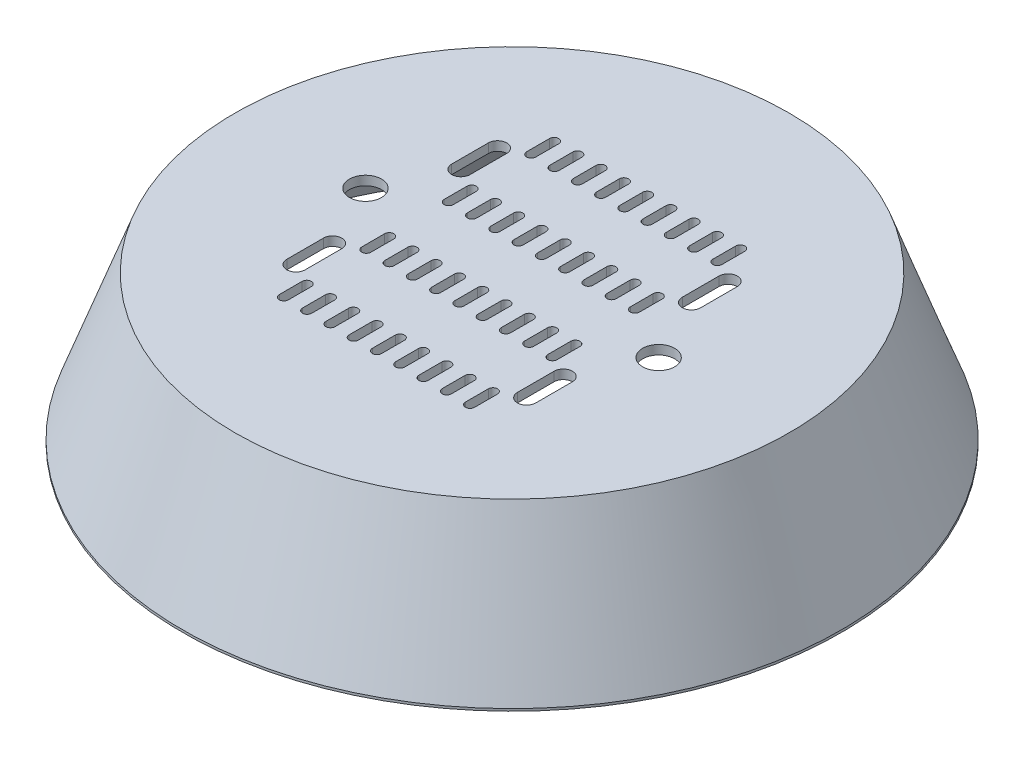
SolidWorks part; units mm, degrees
ref_plane "Alzado" through (0, 0, 0) normal (0, 0, 1) x (1, 0, 0)
ref_plane "Planta" through (0, 0, 0) normal (0, 1, 0) x (1, 0, 0)
ref_plane "Vista lateral" through (0, 0, 0) normal (1, 0, 0) x (0, 0, -1)
sketch "Croquis1" plane through (0, 0, 0) normal (0, 0, 1) x (1, 0, 0)
  line L0 (0, 0) -> (40, 0)
  line L1 (40, 0) -> (59.0809, 0)
  line L2 (59.0809, 0) -> (70, -30)
  line L3 (70, -30) -> (71.9464, -30)
  line L4 (71.9464, -30) -> (71.9464, -29.5)
  line L5 (71.9464, -29.5) -> (60.4813, 2)
  line L6 (0, 2) -> (40, 2)
  line L7 (60.4813, 2) -> (40, 2)
  line L10 (0, 0) -> (0, 2)
  line L13 (40.328, 0) -> (70.6428, 0) construction
  line L14 (70.6428, 0) -> (70.2018, 1.0584) construction
  line L15 (40, 0) -> (40.328, 0) construction
  line L16 (40.328, 2) -> (68.4374, 2) construction
  line L17 (68.4374, 2) -> (68.4374, 2) construction
  line L18 (40, 2) -> (40.328, 2) construction
  dimension "D6" = 0.5
  dimension "D1" = 40
  dimension "D2" = 2
  dimension "D3" = 110
  dimension "D4" = 30
  dimension "D7" = 70
  dimension "D5" = 2
revolve "Revolución1" add sketch "Croquis1" angle 360 about L10
sketch "Croquis3" plane through (0, 2, 0) normal (0, 1, 0) x (1, 0, 0)
  circle A0 centre (-32, 0) radius 3.5
  circle A1 centre (32, 0) radius 3.5
  circle A2 centre (0, 0) radius 32 construction
  dimension "D1" = 7
  dimension "D2" = 64
extrude "Cortar-Extruir1" cut sketch "Croquis3" against normal up to next
sketch "Croquis4" plane through (0, 2, 0) normal (0, 1, 0) x (1, 0, 0)
  line L0 (0, 2.5) -> (0, -2.5) construction
  line L1 (1, 2.5) -> (1, -2.5) construction
  line L2 (-1, 2.5) -> (-1, -2.5) construction
  line L3 (5.08, 2.5) -> (5.08, -2.5) construction
  line L4 (6.08, 2.5) -> (6.08, -2.5) construction
  line L5 (4.08, 2.5) -> (4.08, -2.5) construction
  line L6 (10.16, 2.5) -> (10.16, -2.5) construction
  line L7 (11.16, 2.5) -> (11.16, -2.5) construction
  line L8 (9.16, 2.5) -> (9.16, -2.5) construction
  line L9 (15.24, 2.5) -> (15.24, -2.5) construction
  line L10 (16.24, 2.5) -> (16.24, -2.5) construction
  line L11 (14.24, 2.5) -> (14.24, -2.5) construction
  line L12 (20.32, 2.5) -> (20.32, -2.5) construction
  line L13 (21.32, 2.5) -> (21.32, -2.5) construction
  line L14 (19.32, 2.5) -> (19.32, -2.5) construction
  line L15 (-5.08, 2.5) -> (-5.08, -2.5) construction
  line L16 (-4.08, 2.5) -> (-4.08, -2.5) construction
  line L17 (-6.08, 2.5) -> (-6.08, -2.5) construction
  line L18 (-10.16, 2.5) -> (-10.16, -2.5) construction
  line L19 (-9.16, 2.5) -> (-9.16, -2.5) construction
  line L20 (-11.16, 2.5) -> (-11.16, -2.5) construction
  line L21 (-15.24, 2.5) -> (-15.24, -2.5) construction
  line L22 (-14.24, 2.5) -> (-14.24, -2.5) construction
  line L23 (-16.24, 2.5) -> (-16.24, -2.5) construction
  line L24 (-20.32, 2.5) -> (-20.32, -2.5) construction
  line L25 (-19.32, 2.5) -> (-19.32, -2.5) construction
  line L26 (-21.32, 2.5) -> (-21.32, -2.5) construction
  line L27 (0, 11.5) -> (0, 6.5) construction
  line L28 (1, 11.5) -> (1, 6.5)
  line L29 (-1, 11.5) -> (-1, 6.5)
  line L30 (5.08, 11.5) -> (5.08, 6.5) construction
  line L31 (6.08, 11.5) -> (6.08, 6.5)
  line L32 (4.08, 11.5) -> (4.08, 6.5)
  line L33 (10.16, 11.5) -> (10.16, 6.5) construction
  line L34 (11.16, 11.5) -> (11.16, 6.5)
  line L35 (9.16, 11.5) -> (9.16, 6.5)
  line L36 (15.24, 11.5) -> (15.24, 6.5) construction
  line L37 (16.24, 11.5) -> (16.24, 6.5)
  line L38 (14.24, 11.5) -> (14.24, 6.5)
  line L39 (20.32, 11.5) -> (20.32, 6.5) construction
  line L40 (21.32, 11.5) -> (21.32, 6.5)
  line L41 (19.32, 11.5) -> (19.32, 6.5)
  line L42 (-5.08, 11.5) -> (-5.08, 6.5) construction
  line L43 (-4.08, 11.5) -> (-4.08, 6.5)
  line L44 (-6.08, 11.5) -> (-6.08, 6.5)
  line L45 (-10.16, 11.5) -> (-10.16, 6.5) construction
  line L46 (-9.16, 11.5) -> (-9.16, 6.5)
  line L47 (-11.16, 11.5) -> (-11.16, 6.5)
  line L48 (-15.24, 11.5) -> (-15.24, 6.5) construction
  line L49 (-14.24, 11.5) -> (-14.24, 6.5)
  line L50 (-16.24, 11.5) -> (-16.24, 6.5)
  line L51 (-20.32, 11.5) -> (-20.32, 6.5) construction
  line L52 (-19.32, 11.5) -> (-19.32, 6.5)
  line L53 (-21.32, 11.5) -> (-21.32, 6.5)
  line L54 (0, 20.5) -> (0, 15.5) construction
  line L55 (1, 20.5) -> (1, 15.5) construction
  line L56 (-1, 20.5) -> (-1, 15.5) construction
  line L57 (5.08, 20.5) -> (5.08, 15.5) construction
  line L58 (6.08, 20.5) -> (6.08, 15.5) construction
  line L59 (4.08, 20.5) -> (4.08, 15.5) construction
  line L60 (10.16, 20.5) -> (10.16, 15.5) construction
  line L61 (11.16, 20.5) -> (11.16, 15.5) construction
  line L62 (9.16, 20.5) -> (9.16, 15.5) construction
  line L63 (15.24, 20.5) -> (15.24, 15.5) construction
  line L64 (16.24, 20.5) -> (16.24, 15.5) construction
  line L65 (14.24, 20.5) -> (14.24, 15.5) construction
  line L66 (20.32, 20.5) -> (20.32, 15.5) construction
  line L67 (21.32, 20.5) -> (21.32, 15.5) construction
  line L68 (19.32, 20.5) -> (19.32, 15.5) construction
  line L69 (-5.08, 20.5) -> (-5.08, 15.5) construction
  line L70 (-4.08, 20.5) -> (-4.08, 15.5) construction
  line L71 (-6.08, 20.5) -> (-6.08, 15.5) construction
  line L72 (-10.16, 20.5) -> (-10.16, 15.5) construction
  line L73 (-9.16, 20.5) -> (-9.16, 15.5) construction
  line L74 (-11.16, 20.5) -> (-11.16, 15.5) construction
  line L75 (-15.24, 20.5) -> (-15.24, 15.5) construction
  line L76 (-14.24, 20.5) -> (-14.24, 15.5) construction
  line L77 (-16.24, 20.5) -> (-16.24, 15.5) construction
  line L78 (-20.32, 20.5) -> (-20.32, 15.5) construction
  line L79 (-19.32, 20.5) -> (-19.32, 15.5) construction
  line L80 (-21.32, 20.5) -> (-21.32, 15.5) construction
  line L81 (0, 29.5) -> (0, 24.5) construction
  line L82 (1, 29.5) -> (1, 24.5)
  line L83 (-1, 29.5) -> (-1, 24.5)
  line L84 (5.08, 29.5) -> (5.08, 24.5) construction
  line L85 (6.08, 29.5) -> (6.08, 24.5)
  line L86 (4.08, 29.5) -> (4.08, 24.5)
  line L87 (10.16, 29.5) -> (10.16, 24.5) construction
  line L88 (11.16, 29.5) -> (11.16, 24.5)
  line L89 (9.16, 29.5) -> (9.16, 24.5)
  line L90 (15.24, 29.5) -> (15.24, 24.5) construction
  line L91 (16.24, 29.5) -> (16.24, 24.5)
  line L92 (14.24, 29.5) -> (14.24, 24.5)
  line L93 (20.32, 29.5) -> (20.32, 24.5) construction
  line L94 (21.32, 29.5) -> (21.32, 24.5)
  line L95 (19.32, 29.5) -> (19.32, 24.5)
  line L96 (-5.08, 29.5) -> (-5.08, 24.5) construction
  line L97 (-4.08, 29.5) -> (-4.08, 24.5)
  line L98 (-6.08, 29.5) -> (-6.08, 24.5)
  line L99 (-10.16, 29.5) -> (-10.16, 24.5) construction
  line L100 (-9.16, 29.5) -> (-9.16, 24.5)
  line L101 (-11.16, 29.5) -> (-11.16, 24.5)
  line L102 (-15.24, 29.5) -> (-15.24, 24.5) construction
  line L103 (-14.24, 29.5) -> (-14.24, 24.5)
  line L104 (-16.24, 29.5) -> (-16.24, 24.5)
  line L105 (-20.32, 29.5) -> (-20.32, 24.5) construction
  line L106 (-19.32, 29.5) -> (-19.32, 24.5)
  line L107 (-21.32, 29.5) -> (-21.32, 24.5)
  line L108 (0, -6.5) -> (0, -11.5) construction
  line L109 (1, -6.5) -> (1, -11.5)
  line L110 (-1, -6.5) -> (-1, -11.5)
  line L111 (5.08, -6.5) -> (5.08, -11.5) construction
  line L112 (6.08, -6.5) -> (6.08, -11.5)
  line L113 (4.08, -6.5) -> (4.08, -11.5)
  line L114 (10.16, -6.5) -> (10.16, -11.5) construction
  line L115 (11.16, -6.5) -> (11.16, -11.5)
  line L116 (9.16, -6.5) -> (9.16, -11.5)
  line L117 (15.24, -6.5) -> (15.24, -11.5) construction
  line L118 (16.24, -6.5) -> (16.24, -11.5)
  line L119 (14.24, -6.5) -> (14.24, -11.5)
  line L120 (20.32, -6.5) -> (20.32, -11.5) construction
  line L121 (21.32, -6.5) -> (21.32, -11.5)
  line L122 (19.32, -6.5) -> (19.32, -11.5)
  line L123 (-5.08, -6.5) -> (-5.08, -11.5) construction
  line L124 (-4.08, -6.5) -> (-4.08, -11.5)
  line L125 (-6.08, -6.5) -> (-6.08, -11.5)
  line L126 (-10.16, -6.5) -> (-10.16, -11.5) construction
  line L127 (-9.16, -6.5) -> (-9.16, -11.5)
  line L128 (-11.16, -6.5) -> (-11.16, -11.5)
  line L129 (-15.24, -6.5) -> (-15.24, -11.5) construction
  line L130 (-14.24, -6.5) -> (-14.24, -11.5)
  line L131 (-16.24, -6.5) -> (-16.24, -11.5)
  line L132 (-20.32, -6.5) -> (-20.32, -11.5) construction
  line L133 (-19.32, -6.5) -> (-19.32, -11.5)
  line L134 (-21.32, -6.5) -> (-21.32, -11.5)
  line L135 (0, -15.5) -> (0, -20.5) construction
  line L136 (1, -15.5) -> (1, -20.5) construction
  line L137 (-1, -15.5) -> (-1, -20.5) construction
  line L138 (5.08, -15.5) -> (5.08, -20.5) construction
  line L139 (6.08, -15.5) -> (6.08, -20.5) construction
  line L140 (4.08, -15.5) -> (4.08, -20.5) construction
  line L141 (10.16, -15.5) -> (10.16, -20.5) construction
  line L142 (11.16, -15.5) -> (11.16, -20.5) construction
  line L143 (9.16, -15.5) -> (9.16, -20.5) construction
  line L144 (15.24, -15.5) -> (15.24, -20.5) construction
  line L145 (16.24, -15.5) -> (16.24, -20.5) construction
  line L146 (14.24, -15.5) -> (14.24, -20.5) construction
  line L147 (20.32, -15.5) -> (20.32, -20.5) construction
  line L148 (21.32, -15.5) -> (21.32, -20.5) construction
  line L149 (19.32, -15.5) -> (19.32, -20.5) construction
  line L150 (-5.08, -15.5) -> (-5.08, -20.5) construction
  line L151 (-4.08, -15.5) -> (-4.08, -20.5) construction
  line L152 (-6.08, -15.5) -> (-6.08, -20.5) construction
  line L153 (-10.16, -15.5) -> (-10.16, -20.5) construction
  line L154 (-9.16, -15.5) -> (-9.16, -20.5) construction
  line L155 (-11.16, -15.5) -> (-11.16, -20.5) construction
  line L156 (-15.24, -15.5) -> (-15.24, -20.5) construction
  line L157 (-14.24, -15.5) -> (-14.24, -20.5) construction
  line L158 (-16.24, -15.5) -> (-16.24, -20.5) construction
  line L159 (-20.32, -15.5) -> (-20.32, -20.5) construction
  line L160 (-19.32, -15.5) -> (-19.32, -20.5) construction
  line L161 (-21.32, -15.5) -> (-21.32, -20.5) construction
  line L162 (0, -24.5) -> (0, -29.5) construction
  line L163 (1, -24.5) -> (1, -29.5)
  line L164 (-1, -24.5) -> (-1, -29.5)
  line L165 (5.08, -24.5) -> (5.08, -29.5) construction
  line L166 (6.08, -24.5) -> (6.08, -29.5)
  line L167 (4.08, -24.5) -> (4.08, -29.5)
  line L168 (10.16, -24.5) -> (10.16, -29.5) construction
  line L169 (11.16, -24.5) -> (11.16, -29.5)
  line L170 (9.16, -24.5) -> (9.16, -29.5)
  line L171 (15.24, -24.5) -> (15.24, -29.5) construction
  line L172 (16.24, -24.5) -> (16.24, -29.5)
  line L173 (14.24, -24.5) -> (14.24, -29.5)
  line L174 (20.32, -24.5) -> (20.32, -29.5) construction
  line L175 (21.32, -24.5) -> (21.32, -29.5)
  line L176 (19.32, -24.5) -> (19.32, -29.5)
  line L177 (-5.08, -24.5) -> (-5.08, -29.5) construction
  line L178 (-4.08, -24.5) -> (-4.08, -29.5)
  line L179 (-6.08, -24.5) -> (-6.08, -29.5)
  line L180 (-10.16, -24.5) -> (-10.16, -29.5) construction
  line L181 (-9.16, -24.5) -> (-9.16, -29.5)
  line L182 (-11.16, -24.5) -> (-11.16, -29.5)
  line L183 (-15.24, -24.5) -> (-15.24, -29.5) construction
  line L184 (-14.24, -24.5) -> (-14.24, -29.5)
  line L185 (-16.24, -24.5) -> (-16.24, -29.5)
  line L186 (-20.32, -24.5) -> (-20.32, -29.5) construction
  line L187 (-19.32, -24.5) -> (-19.32, -29.5)
  line L188 (-21.32, -24.5) -> (-21.32, -29.5)
  arc A0 (1, 2.5) -> (-1, 2.5) centre (0, 2.5) ccw construction
  arc A1 (-1, -2.5) -> (1, -2.5) centre (0, -2.5) ccw construction
  arc A2 (6.08, 2.5) -> (4.08, 2.5) centre (5.08, 2.5) ccw construction
  arc A3 (4.08, -2.5) -> (6.08, -2.5) centre (5.08, -2.5) ccw construction
  arc A4 (11.16, 2.5) -> (9.16, 2.5) centre (10.16, 2.5) ccw construction
  arc A5 (9.16, -2.5) -> (11.16, -2.5) centre (10.16, -2.5) ccw construction
  arc A6 (16.24, 2.5) -> (14.24, 2.5) centre (15.24, 2.5) ccw construction
  arc A7 (14.24, -2.5) -> (16.24, -2.5) centre (15.24, -2.5) ccw construction
  arc A8 (21.32, 2.5) -> (19.32, 2.5) centre (20.32, 2.5) ccw construction
  arc A9 (19.32, -2.5) -> (21.32, -2.5) centre (20.32, -2.5) ccw construction
  arc A10 (-4.08, 2.5) -> (-6.08, 2.5) centre (-5.08, 2.5) ccw construction
  arc A11 (-6.08, -2.5) -> (-4.08, -2.5) centre (-5.08, -2.5) ccw construction
  arc A12 (-9.16, 2.5) -> (-11.16, 2.5) centre (-10.16, 2.5) ccw construction
  arc A13 (-11.16, -2.5) -> (-9.16, -2.5) centre (-10.16, -2.5) ccw construction
  arc A14 (-14.24, 2.5) -> (-16.24, 2.5) centre (-15.24, 2.5) ccw construction
  arc A15 (-16.24, -2.5) -> (-14.24, -2.5) centre (-15.24, -2.5) ccw construction
  arc A16 (-19.32, 2.5) -> (-21.32, 2.5) centre (-20.32, 2.5) ccw construction
  arc A17 (-21.32, -2.5) -> (-19.32, -2.5) centre (-20.32, -2.5) ccw construction
  arc A18 (1, 11.5) -> (-1, 11.5) centre (0, 11.5) ccw
  arc A19 (-1, 6.5) -> (1, 6.5) centre (0, 6.5) ccw
  arc A20 (6.08, 11.5) -> (4.08, 11.5) centre (5.08, 11.5) ccw
  arc A21 (4.08, 6.5) -> (6.08, 6.5) centre (5.08, 6.5) ccw
  arc A22 (11.16, 11.5) -> (9.16, 11.5) centre (10.16, 11.5) ccw
  arc A23 (9.16, 6.5) -> (11.16, 6.5) centre (10.16, 6.5) ccw
  arc A24 (16.24, 11.5) -> (14.24, 11.5) centre (15.24, 11.5) ccw
  arc A25 (14.24, 6.5) -> (16.24, 6.5) centre (15.24, 6.5) ccw
  arc A26 (21.32, 11.5) -> (19.32, 11.5) centre (20.32, 11.5) ccw
  arc A27 (19.32, 6.5) -> (21.32, 6.5) centre (20.32, 6.5) ccw
  arc A28 (-4.08, 11.5) -> (-6.08, 11.5) centre (-5.08, 11.5) ccw
  arc A29 (-6.08, 6.5) -> (-4.08, 6.5) centre (-5.08, 6.5) ccw
  arc A30 (-9.16, 11.5) -> (-11.16, 11.5) centre (-10.16, 11.5) ccw
  arc A31 (-11.16, 6.5) -> (-9.16, 6.5) centre (-10.16, 6.5) ccw
  arc A32 (-14.24, 11.5) -> (-16.24, 11.5) centre (-15.24, 11.5) ccw
  arc A33 (-16.24, 6.5) -> (-14.24, 6.5) centre (-15.24, 6.5) ccw
  arc A34 (-19.32, 11.5) -> (-21.32, 11.5) centre (-20.32, 11.5) ccw
  arc A35 (-21.32, 6.5) -> (-19.32, 6.5) centre (-20.32, 6.5) ccw
  arc A36 (1, 20.5) -> (-1, 20.5) centre (0, 20.5) ccw construction
  arc A37 (-1, 15.5) -> (1, 15.5) centre (0, 15.5) ccw construction
  arc A38 (6.08, 20.5) -> (4.08, 20.5) centre (5.08, 20.5) ccw construction
  arc A39 (4.08, 15.5) -> (6.08, 15.5) centre (5.08, 15.5) ccw construction
  arc A40 (11.16, 20.5) -> (9.16, 20.5) centre (10.16, 20.5) ccw construction
  arc A41 (9.16, 15.5) -> (11.16, 15.5) centre (10.16, 15.5) ccw construction
  arc A42 (16.24, 20.5) -> (14.24, 20.5) centre (15.24, 20.5) ccw construction
  arc A43 (14.24, 15.5) -> (16.24, 15.5) centre (15.24, 15.5) ccw construction
  arc A44 (21.32, 20.5) -> (19.32, 20.5) centre (20.32, 20.5) ccw construction
  arc A45 (19.32, 15.5) -> (21.32, 15.5) centre (20.32, 15.5) ccw construction
  arc A46 (-4.08, 20.5) -> (-6.08, 20.5) centre (-5.08, 20.5) ccw construction
  arc A47 (-6.08, 15.5) -> (-4.08, 15.5) centre (-5.08, 15.5) ccw construction
  arc A48 (-9.16, 20.5) -> (-11.16, 20.5) centre (-10.16, 20.5) ccw construction
  arc A49 (-11.16, 15.5) -> (-9.16, 15.5) centre (-10.16, 15.5) ccw construction
  arc A50 (-14.24, 20.5) -> (-16.24, 20.5) centre (-15.24, 20.5) ccw construction
  arc A51 (-16.24, 15.5) -> (-14.24, 15.5) centre (-15.24, 15.5) ccw construction
  arc A52 (-19.32, 20.5) -> (-21.32, 20.5) centre (-20.32, 20.5) ccw construction
  arc A53 (-21.32, 15.5) -> (-19.32, 15.5) centre (-20.32, 15.5) ccw construction
  arc A54 (1, 29.5) -> (-1, 29.5) centre (0, 29.5) ccw
  arc A55 (-1, 24.5) -> (1, 24.5) centre (0, 24.5) ccw
  arc A56 (6.08, 29.5) -> (4.08, 29.5) centre (5.08, 29.5) ccw
  arc A57 (4.08, 24.5) -> (6.08, 24.5) centre (5.08, 24.5) ccw
  arc A58 (11.16, 29.5) -> (9.16, 29.5) centre (10.16, 29.5) ccw
  arc A59 (9.16, 24.5) -> (11.16, 24.5) centre (10.16, 24.5) ccw
  arc A60 (16.24, 29.5) -> (14.24, 29.5) centre (15.24, 29.5) ccw
  arc A61 (14.24, 24.5) -> (16.24, 24.5) centre (15.24, 24.5) ccw
  arc A62 (21.32, 29.5) -> (19.32, 29.5) centre (20.32, 29.5) ccw
  arc A63 (19.32, 24.5) -> (21.32, 24.5) centre (20.32, 24.5) ccw
  arc A64 (-4.08, 29.5) -> (-6.08, 29.5) centre (-5.08, 29.5) ccw
  arc A65 (-6.08, 24.5) -> (-4.08, 24.5) centre (-5.08, 24.5) ccw
  arc A66 (-9.16, 29.5) -> (-11.16, 29.5) centre (-10.16, 29.5) ccw
  arc A67 (-11.16, 24.5) -> (-9.16, 24.5) centre (-10.16, 24.5) ccw
  arc A68 (-14.24, 29.5) -> (-16.24, 29.5) centre (-15.24, 29.5) ccw
  arc A69 (-16.24, 24.5) -> (-14.24, 24.5) centre (-15.24, 24.5) ccw
  arc A70 (-19.32, 29.5) -> (-21.32, 29.5) centre (-20.32, 29.5) ccw
  arc A71 (-21.32, 24.5) -> (-19.32, 24.5) centre (-20.32, 24.5) ccw
  arc A72 (1, -6.5) -> (-1, -6.5) centre (0, -6.5) ccw
  arc A73 (-1, -11.5) -> (1, -11.5) centre (0, -11.5) ccw
  arc A74 (6.08, -6.5) -> (4.08, -6.5) centre (5.08, -6.5) ccw
  arc A75 (4.08, -11.5) -> (6.08, -11.5) centre (5.08, -11.5) ccw
  arc A76 (11.16, -6.5) -> (9.16, -6.5) centre (10.16, -6.5) ccw
  arc A77 (9.16, -11.5) -> (11.16, -11.5) centre (10.16, -11.5) ccw
  arc A78 (16.24, -6.5) -> (14.24, -6.5) centre (15.24, -6.5) ccw
  arc A79 (14.24, -11.5) -> (16.24, -11.5) centre (15.24, -11.5) ccw
  arc A80 (21.32, -6.5) -> (19.32, -6.5) centre (20.32, -6.5) ccw
  arc A81 (19.32, -11.5) -> (21.32, -11.5) centre (20.32, -11.5) ccw
  arc A82 (-4.08, -6.5) -> (-6.08, -6.5) centre (-5.08, -6.5) ccw
  arc A83 (-6.08, -11.5) -> (-4.08, -11.5) centre (-5.08, -11.5) ccw
  arc A84 (-9.16, -6.5) -> (-11.16, -6.5) centre (-10.16, -6.5) ccw
  arc A85 (-11.16, -11.5) -> (-9.16, -11.5) centre (-10.16, -11.5) ccw
  arc A86 (-14.24, -6.5) -> (-16.24, -6.5) centre (-15.24, -6.5) ccw
  arc A87 (-16.24, -11.5) -> (-14.24, -11.5) centre (-15.24, -11.5) ccw
  arc A88 (-19.32, -6.5) -> (-21.32, -6.5) centre (-20.32, -6.5) ccw
  arc A89 (-21.32, -11.5) -> (-19.32, -11.5) centre (-20.32, -11.5) ccw
  arc A90 (1, -15.5) -> (-1, -15.5) centre (0, -15.5) ccw construction
  arc A91 (-1, -20.5) -> (1, -20.5) centre (0, -20.5) ccw construction
  arc A92 (6.08, -15.5) -> (4.08, -15.5) centre (5.08, -15.5) ccw construction
  arc A93 (4.08, -20.5) -> (6.08, -20.5) centre (5.08, -20.5) ccw construction
  arc A94 (11.16, -15.5) -> (9.16, -15.5) centre (10.16, -15.5) ccw construction
  arc A95 (9.16, -20.5) -> (11.16, -20.5) centre (10.16, -20.5) ccw construction
  arc A96 (16.24, -15.5) -> (14.24, -15.5) centre (15.24, -15.5) ccw construction
  arc A97 (14.24, -20.5) -> (16.24, -20.5) centre (15.24, -20.5) ccw construction
  arc A98 (21.32, -15.5) -> (19.32, -15.5) centre (20.32, -15.5) ccw construction
  arc A99 (19.32, -20.5) -> (21.32, -20.5) centre (20.32, -20.5) ccw construction
  arc A100 (-4.08, -15.5) -> (-6.08, -15.5) centre (-5.08, -15.5) ccw construction
  arc A101 (-6.08, -20.5) -> (-4.08, -20.5) centre (-5.08, -20.5) ccw construction
  arc A102 (-9.16, -15.5) -> (-11.16, -15.5) centre (-10.16, -15.5) ccw construction
  arc A103 (-11.16, -20.5) -> (-9.16, -20.5) centre (-10.16, -20.5) ccw construction
  arc A104 (-14.24, -15.5) -> (-16.24, -15.5) centre (-15.24, -15.5) ccw construction
  arc A105 (-16.24, -20.5) -> (-14.24, -20.5) centre (-15.24, -20.5) ccw construction
  arc A106 (-19.32, -15.5) -> (-21.32, -15.5) centre (-20.32, -15.5) ccw construction
  arc A107 (-21.32, -20.5) -> (-19.32, -20.5) centre (-20.32, -20.5) ccw construction
  arc A108 (1, -24.5) -> (-1, -24.5) centre (0, -24.5) ccw
  arc A109 (-1, -29.5) -> (1, -29.5) centre (0, -29.5) ccw
  arc A110 (6.08, -24.5) -> (4.08, -24.5) centre (5.08, -24.5) ccw
  arc A111 (4.08, -29.5) -> (6.08, -29.5) centre (5.08, -29.5) ccw
  arc A112 (11.16, -24.5) -> (9.16, -24.5) centre (10.16, -24.5) ccw
  arc A113 (9.16, -29.5) -> (11.16, -29.5) centre (10.16, -29.5) ccw
  arc A114 (16.24, -24.5) -> (14.24, -24.5) centre (15.24, -24.5) ccw
  arc A115 (14.24, -29.5) -> (16.24, -29.5) centre (15.24, -29.5) ccw
  arc A116 (21.32, -24.5) -> (19.32, -24.5) centre (20.32, -24.5) ccw
  arc A117 (19.32, -29.5) -> (21.32, -29.5) centre (20.32, -29.5) ccw
  arc A118 (-4.08, -24.5) -> (-6.08, -24.5) centre (-5.08, -24.5) ccw
  arc A119 (-6.08, -29.5) -> (-4.08, -29.5) centre (-5.08, -29.5) ccw
  arc A120 (-9.16, -24.5) -> (-11.16, -24.5) centre (-10.16, -24.5) ccw
  arc A121 (-11.16, -29.5) -> (-9.16, -29.5) centre (-10.16, -29.5) ccw
  arc A122 (-14.24, -24.5) -> (-16.24, -24.5) centre (-15.24, -24.5) ccw
  arc A123 (-16.24, -29.5) -> (-14.24, -29.5) centre (-15.24, -29.5) ccw
  arc A124 (-19.32, -24.5) -> (-21.32, -24.5) centre (-20.32, -24.5) ccw
  arc A125 (-21.32, -29.5) -> (-19.32, -29.5) centre (-20.32, -29.5) ccw
  point P2 (0, 0)
  point P11 (5.08, 0)
  point P20 (10.16, 0)
  point P27 (15.24, 0)
  point P34 (20.32, 0)
  point P40 (-5.08, 0)
  point P47 (-10.16, 0)
  point P54 (-15.24, 0)
  point P61 (-20.32, 0)
  point P68 (0, 9)
  point P76 (5.08, 9)
  point P83 (10.16, 9)
  point P90 (15.24, 9)
  point P97 (20.32, 9)
  point P103 (-5.08, 9)
  point P110 (-10.16, 9)
  point P117 (-15.24, 9)
  point P124 (-20.32, 9)
  point P131 (0, 18)
  point P139 (5.08, 18)
  point P146 (10.16, 18)
  point P153 (15.24, 18)
  point P160 (20.32, 18)
  point P166 (-5.08, 18)
  point P173 (-10.16, 18)
  point P180 (-15.24, 18)
  point P187 (-20.32, 18)
  point P194 (0, 27)
  point P202 (5.08, 27)
  point P209 (10.16, 27)
  point P216 (15.24, 27)
  point P223 (20.32, 27)
  point P229 (-5.08, 27)
  point P236 (-10.16, 27)
  point P243 (-15.24, 27)
  point P250 (-20.32, 27)
  point P257 (0, -9)
  point P265 (5.08, -9)
  point P272 (10.16, -9)
  point P279 (15.24, -9)
  point P286 (20.32, -9)
  point P292 (-5.08, -9)
  point P299 (-10.16, -9)
  point P306 (-15.24, -9)
  point P313 (-20.32, -9)
  point P320 (0, -18)
  point P328 (5.08, -18)
  point P335 (10.16, -18)
  point P342 (15.24, -18)
  point P349 (20.32, -18)
  point P355 (-5.08, -18)
  point P362 (-10.16, -18)
  point P369 (-15.24, -18)
  point P376 (-20.32, -18)
  point P383 (0, -27)
  point P391 (5.08, -27)
  point P398 (10.16, -27)
  point P405 (15.24, -27)
  point P412 (20.32, -27)
  point P418 (-5.08, -27)
  point P425 (-10.16, -27)
  point P432 (-15.24, -27)
  point P439 (-20.32, -27)
  dimension "D2" = 1
  dimension "D1" = 5
  dimension "D3" = 5
  dimension "D7" = 9
  dimension "D4" = 5
  dimension "D5" = 4
  dimension "D6" = 4
extrude "Cortar-Extruir2" cut sketch "Croquis4" against normal up to next (2 mm away)
sketch "Croquis5" plane through (0, 0, 0) normal (0, 1, 0) x (1, 0, 0)
  circle A0 centre (-32, 0) radius 7.5
  circle A1 centre (32, 0) radius 7.5
  circle A2 centre (32, 0) radius 3.5 construction
  circle A3 centre (-32, 0) radius 3.5 construction
  circle A4 centre (32, 0) radius 3.5
  circle A5 centre (-32, 0) radius 3.5
  dimension "D1" = 15
extrude "Saliente-Extruir1" add sketch "Croquis5" along normal blind 2
ref_axis "Eje1" through (-32, 0, 0) along (0, 1, 0)
ref_plane "Plano1" through (-32, 0, 0) normal (1, 0, 0) x (0, 0, -1)
sketch "Croquis12" plane through (0, 2, 0) normal (0, 1, 0) x (1, 0, 0)
  line L0 (-25.1708, 22) -> (-25.1708, 14) construction
  line L1 (-23.1708, 22) -> (-23.1708, 14)
  line L2 (-27.1708, 22) -> (-27.1708, 14)
  line L3 (0, 0) -> (-40.8607, 0) construction
  line L4 (0, 0) -> (0, 34.9959) construction
  line L5 (25.1708, 22) -> (25.1708, 14) construction
  line L6 (23.1708, 22) -> (23.1708, 14)
  line L7 (27.1708, 22) -> (27.1708, 14)
  line L8 (-25.1708, -22) -> (-25.1708, -14) construction
  line L9 (-23.1708, -22) -> (-23.1708, -14)
  line L10 (-27.1708, -22) -> (-27.1708, -14)
  line L11 (25.1708, -22) -> (25.1708, -14) construction
  line L12 (23.1708, -22) -> (23.1708, -14)
  line L13 (27.1708, -22) -> (27.1708, -14)
  arc A0 (-23.1708, 22) -> (-27.1708, 22) centre (-25.1708, 22) ccw
  arc A1 (-27.1708, 14) -> (-23.1708, 14) centre (-25.1708, 14) ccw
  arc A3 (23.1708, 22) -> (27.1708, 22) centre (25.1708, 22) cw
  arc A4 (27.1708, 14) -> (23.1708, 14) centre (25.1708, 14) cw
  arc A5 (-23.1708, -22) -> (-27.1708, -22) centre (-25.1708, -22) cw
  arc A6 (-27.1708, -14) -> (-23.1708, -14) centre (-25.1708, -14) cw
  arc A7 (23.1708, -22) -> (27.1708, -22) centre (25.1708, -22) ccw
  arc A8 (27.1708, -14) -> (23.1708, -14) centre (25.1708, -14) ccw
  point P2 (-25.1708, 18)
  point P15 (25.1708, 18)
  point P22 (-25.1708, -18)
  point P29 (25.1708, -18)
  dimension "D2" = 2
  dimension "D3" = 18
  dimension "D1" = 8
extrude "Cortar-Extruir3" cut sketch "Croquis12" against normal up to next
sketch "Croquis13" plane through (0, -30, 0) normal (0, -1, 0) x (1, 0, 0)
  line L0 (0, 0) -> (0, -81.8521) construction
  line L1 (-0.1, -59.0808) -> (-0.1, -71.9463)
  line L2 (0.1, -59.0808) -> (0.1, -71.9463)
  line L4 (0.1, 0) -> (0.1, -81.8521) construction
  line L5 (-0.1, 0) -> (-0.1, -81.8521) construction
  circle A0 centre (0, 0) radius 59.0809 construction
  arc A1 (-0.1, -59.0808) -> (0.1, -59.0808) centre (0, 0) ccw
  circle A2 centre (0, 0) radius 71.9464 construction
  arc A3 (-0.1, -71.9463) -> (0.1, -71.9463) centre (0, 0) ccw
  dimension "D1" = 0.1
  dimension "D2" = 0.1
extrude "Cortar-Extruir4" [suppressed] cut sketch "Croquis13" against normal up to surface (30 mm away)
